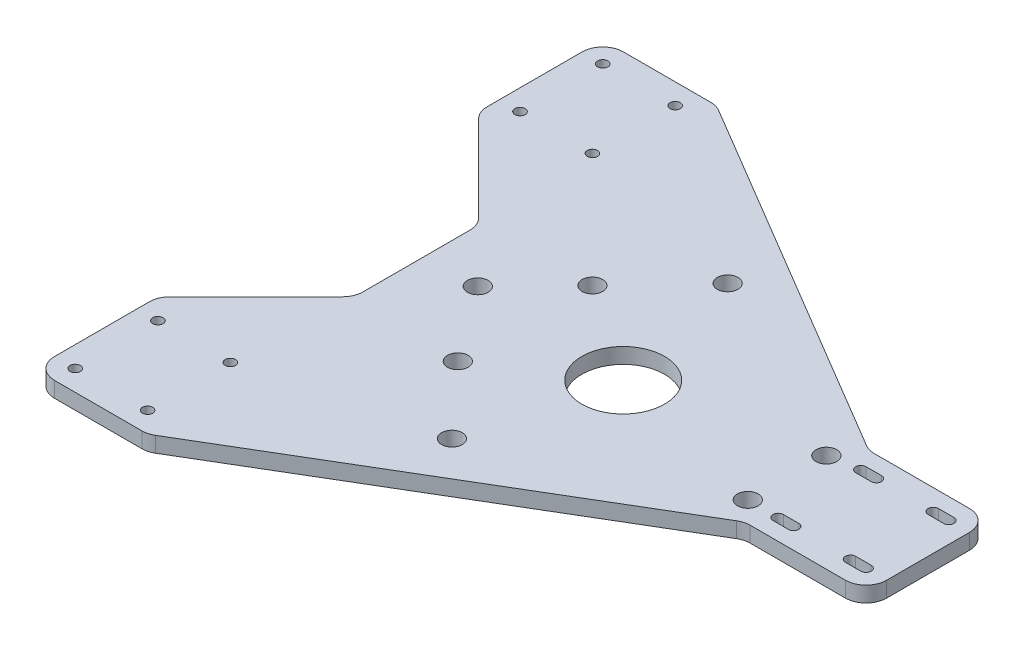
SolidWorks part; units mm, degrees
material "6061-O (SS)"
ref_plane "Plan de face" through (0, 0, 0) normal (0, 0, 1) x (1, 0, 0)
ref_plane "Plan de dessus" through (0, 0, 0) normal (0, 1, 0) x (1, 0, 0)
ref_plane "Plan de droite" through (0, 0, 0) normal (1, 0, 0) x (0, 0, -1)
sketch "Esquisse1" plane through (0, 0, 0) normal (0, 1, 0) x (1, 0, 0)
  line L1 (58.95, -55) -> (-58.95, -55)
  line L2 (58.95, -55) -> (58.95, 55)
  line L3 (58.95, 55) -> (-58.95, 55)
  line L4 (-58.95, -55) -> (-58.95, 55)
  line L5 (58.95, -55) -> (-58.95, 55) construction
  line L6 (58.95, 55) -> (-58.95, -55) construction
  point P0 (0, 0)
  dimension "D1" = 110
  dimension "D2" = 117.9
extrude "Boss.-Extru.1" add sketch "Esquisse1" along normal blind 3
sketch "Esquisse2" plane through (0, 0, 0) normal (0, 1, 0) x (1, 0, 0)
  line L0 (-58.95, -55) -> (58.95, -55) construction
  line L1 (-54.95, -35) -> (-40.95, -35) construction
  line L2 (-54.95, -35) -> (-54.95, -51) construction
  line L3 (-54.95, -51) -> (-40.95, -51) construction
  line L4 (-40.95, -35) -> (-40.95, -51) construction
  line L5 (-54.95, -35) -> (-40.95, -51) construction
  line L6 (-54.95, -51) -> (-40.95, -35) construction
  line L7 (-58.95, 55) -> (-58.95, -55) construction
  line L8 (0, 0) -> (-58.95, 0) construction
  line L9 (-54.95, 51) -> (-40.95, 35) construction
  line L10 (-54.95, 35) -> (-40.95, 51) construction
  line L11 (-40.95, 35) -> (-40.95, 51) construction
  line L12 (-54.95, 51) -> (-40.95, 51) construction
  line L13 (-54.95, 35) -> (-54.95, 51) construction
  line L14 (-54.95, 35) -> (-40.95, 35) construction
  line L15 (46.45, 0) -> (53.45, 8) construction
  line L16 (39.45, 8) -> (53.45, 8) construction
  line L17 (39.45, 8) -> (39.45, -8) construction
  line L18 (39.45, -8) -> (53.45, -8) construction
  line L19 (53.45, 8) -> (53.45, -8) construction
  line L20 (39.45, 8) -> (46.45, 0) construction
  line L21 (39.45, -8) -> (46.45, 0) construction
  line L22 (46.45, 0) -> (53.45, -8) construction
  line L23 (0, 0) -> (58.95, 0) construction
  line L24 (58.95, -55) -> (58.95, 55) construction
  line L25 (58.95, 12) -> (35.45, 12)
  line L26 (35.45, 12) -> (-36.95, 55)
  line L27 (58.95, 55) -> (-58.95, 55) construction
  line L28 (-36.95, 55) -> (58.95, 55)
  line L29 (58.95, 55) -> (58.95, 12)
  line L30 (58.95, -12) -> (35.45, -12)
  line L31 (58.95, -55) -> (58.95, -12)
  line L32 (-36.95, -55) -> (58.95, -55)
  line L33 (35.45, -12) -> (-36.95, -55)
  line L34 (-58.95, -31) -> (-39.95, -12)
  line L35 (-39.95, -12) -> (-39.95, 12)
  line L36 (-39.95, 12) -> (-58.95, 31)
  line L37 (-58.95, 31) -> (-58.95, -31)
  line L38 (37.95, 8) -> (40.95, 8) construction
  line L39 (37.95, 9) -> (40.95, 9)
  line L40 (37.95, 7) -> (40.95, 7)
  line L41 (54.95, 8) -> (51.95, 8) construction
  line L42 (54.95, 7) -> (51.95, 7)
  line L43 (54.95, 9) -> (51.95, 9)
  line L44 (37.95, -8) -> (40.95, -8) construction
  line L45 (37.95, -7) -> (40.95, -7)
  line L46 (37.95, -9) -> (40.95, -9)
  line L47 (54.95, -8) -> (51.95, -8) construction
  line L48 (54.95, -9) -> (51.95, -9)
  line L49 (54.95, -7) -> (51.95, -7)
  circle A0 centre (-40.95, -35) radius 1
  circle A1 centre (-54.95, -35) radius 1
  circle A2 centre (-54.95, -51) radius 1
  circle A3 centre (-40.95, -51) radius 1
  circle A4 centre (-40.95, 51) radius 1
  circle A5 centre (-54.95, 51) radius 1
  circle A6 centre (-54.95, 35) radius 1
  circle A7 centre (-40.95, 35) radius 1
  arc A12 (37.95, 9) -> (37.95, 7) centre (37.95, 8) ccw
  arc A13 (40.95, 7) -> (40.95, 9) centre (40.95, 8) ccw
  arc A14 (54.95, 7) -> (54.95, 9) centre (54.95, 8) ccw
  arc A15 (51.95, 9) -> (51.95, 7) centre (51.95, 8) ccw
  arc A16 (37.95, -7) -> (37.95, -9) centre (37.95, -8) ccw
  arc A17 (40.95, -9) -> (40.95, -7) centre (40.95, -8) ccw
  arc A18 (54.95, -9) -> (54.95, -7) centre (54.95, -8) ccw
  arc A19 (51.95, -7) -> (51.95, -9) centre (51.95, -8) ccw
  point P0 (-47.95, -43)
  point P25 (-47.95, 43)
  point P26 (46.45, 0)
  point P33 (39.45, 8)
  point P52 (-39.95, 0)
  point P58 (53.45, 8)
  point P65 (39.45, -8)
  point P72 (53.45, -8)
  dimension "D3" = 2
  dimension "D4" = 4
  dimension "D5" = 4
  dimension "D6" = 1
  dimension "D1" = 16
  dimension "D2" = 14
  dimension "D7" = 14
  dimension "D8" = 16
  dimension "D9" = 5.5
  dimension "D10" = 4
  dimension "D11" = 4
  dimension "D12" = 4
  dimension "D13" = 4
  dimension "D14" = 4
  dimension "D15" = 4
  dimension "D16" = 1
  dimension "D17" = 1.5
extrude "Enlèv. mat.-Extru.1" cut sketch "Esquisse2" along normal through all
fillet "Congé1" radius 4 12 edges at (35.45, 1.5, 12) (58.95, 1.5, 12) (58.95, 1.5, -12) (35.45, 1.5, -12) (-36.95, 1.5, -55) (-58.95, 1.5, -55) (-58.95, 1.5, -31) (-39.95, 1.5, -12) (-39.95, 1.5, 12) (-58.95, 1.5, 31) (-58.95, 1.5, 55) (-36.95, 1.5, 55)
sketch "Esquisse3" plane through (0, 0, 0) normal (0, 1, 0) x (1, 0, 0)
  line L1 (11, -11) -> (-11, -11) construction
  line L2 (11, -11) -> (11, 11) construction
  line L3 (11, 11) -> (-11, 11) construction
  line L4 (-11, -11) -> (-11, 11) construction
  line L5 (11, -11) -> (-11, 11) construction
  line L6 (11, 11) -> (-11, -11) construction
  line L7 (-11.5, 11) -> (-10.5, 11) construction
  line L8 (-11.5, 13) -> (-10.5, 13)
  line L9 (-11.5, 9) -> (-10.5, 9)
  line L10 (0, 0) -> (-11, 0) construction
  line L11 (0, 0) -> (0, 11) construction
  line L12 (11.5, 11) -> (10.5, 11) construction
  line L13 (11.5, 13) -> (10.5, 13)
  line L14 (11.5, 9) -> (10.5, 9)
  line L15 (11.5, -11) -> (10.5, -11) construction
  line L16 (11.5, -13) -> (10.5, -13)
  line L17 (11.5, -9) -> (10.5, -9)
  line L18 (-11.5, -11) -> (-10.5, -11) construction
  line L19 (-11.5, -13) -> (-10.5, -13)
  line L20 (-11.5, -9) -> (-10.5, -9)
  arc A4 (-11.5, 13) -> (-11.5, 9) centre (-11.5, 11) ccw
  arc A5 (-10.5, 9) -> (-10.5, 13) centre (-10.5, 11) ccw
  arc A6 (11.5, 13) -> (11.5, 9) centre (11.5, 11) cw
  arc A7 (10.5, 9) -> (10.5, 13) centre (10.5, 11) cw
  arc A8 (11.5, -13) -> (11.5, -9) centre (11.5, -11) ccw
  arc A9 (10.5, -9) -> (10.5, -13) centre (10.5, -11) ccw
  arc A10 (-11.5, -13) -> (-11.5, -9) centre (-11.5, -11) cw
  arc A11 (-10.5, -9) -> (-10.5, -13) centre (-10.5, -11) cw
  circle A12 centre (0, 0) radius 8
  point P0 (0, 0)
  point P8 (-11, 11)
  point P22 (11, 11)
  point P29 (11, -11)
  point P36 (-11, -11)
  dimension "D3" = 2
  dimension "D6" = 16
  dimension "D1" = 22
  dimension "D2" = 22
  dimension "D5" = 0.5
extrude "Enlèv. mat.-Extru.2" cut sketch "Esquisse3" along normal through all contours A12
sketch "Esquisse5" plane through (0, 0, 0) normal (0, 0, 1) x (1, 0, 0)
  line L0 (0, 0) -> (0, 0.489) construction
sketch "Esquisse6" plane through (0, 0, 0) normal (0, -1, 0) x (1, 0, 0)
  circle A0 centre (32.2583, -7.0159) radius 2
  circle A1 centre (32.0732, 7.983) radius 2
  circle A2 centre (-6.775, 26.3319) radius 2
  circle A3 centre (-6.1253, -26.3179) radius 2
  circle A4 centre (-18.8425, -12.8835) radius 2
  circle A5 centre (-19.1596, 12.8146) radius 2
  circle A6 centre (-29.7817, -1.6676) radius 2
extrude "Enlèv. mat.-Extru.3" cut sketch "Esquisse6" against normal through all
